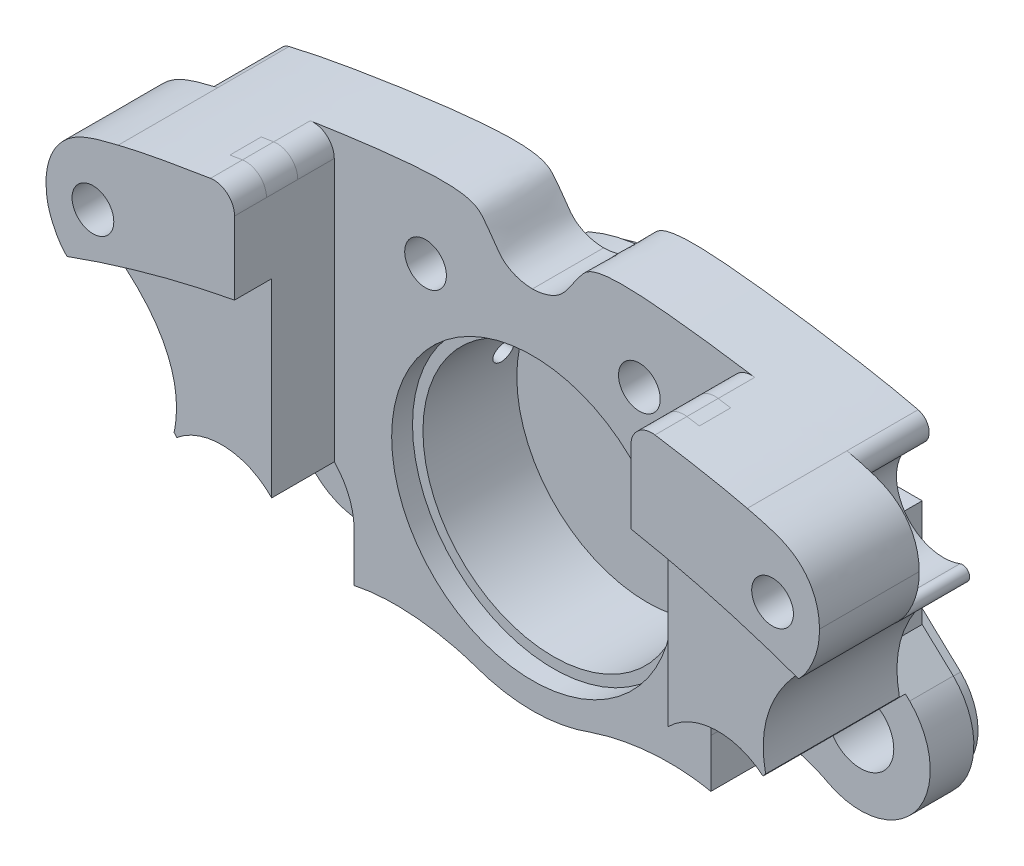
SolidWorks part; units mm, degrees
material "Plain Carbon Steel"
ref_plane "Front Plane" through (0, 0, 0) normal (0, 0, 1) x (1, 0, 0)
ref_plane "Top Plane" through (0, 0, 0) normal (0, 1, 0) x (1, 0, 0)
ref_plane "Right Plane" through (0, 0, 0) normal (1, 0, 0) x (0, 0, -1)
sketch "Sketch1" plane through (0, 0, 0) normal (0, 0, 1) x (1, 0, 0)
  circle A0 centre (0, 0) radius 9.7028
  dimension "D1" = 19.4056
extrude "Boss-Extrude1" add sketch "Sketch1" along normal blind 4.8514
sketch "Sketch2" plane through (0, 0, 4.8514) normal (0, 0, 1) x (1, 0, 0)
  line L0 (0, 15.875) -> (0, -12.065) construction
  line L1 (-30.226, -12.065) -> (30.226, -12.065) construction
  line L2 (-13.4704, 13.4704) -> (-35.3447, -6.9463)
  line L3 (13.4704, 13.4704) -> (35.3447, -6.9463)
  line L4 (0, 0) -> (13.4704, 13.4704) construction
  line L5 (0, 0) -> (-13.4704, 13.4704) construction
  line L8 (15.9939, -16.129) -> (17.3992, -16.129) construction
  line L14 (-17.3992, -16.129) -> (-15.9939, -16.129) construction
  arc A1 (-6.8392, -17.78) -> (6.8392, -17.78) centre (0, 0) ccw
  arc A4 (26.7503, -18.415) -> (35.3447, -6.9463) centre (30.226, -12.065) ccw
  arc A5 (-35.3447, -6.9463) -> (-26.7503, -18.415) centre (-30.226, -12.065) ccw
  arc A7 (13.4704, 13.4704) -> (-13.4704, 13.4704) centre (0, 0) ccw
  spline S0 degree 3 poles (-26.7503, -18.415) (-20.9125, -15.2196) (-12.826, -15.7036) (-6.8392, -17.78) knots 0 0 0 0 1 1 1 1
  spline S1 degree 3 poles (26.7503, -18.415) (20.9125, -15.2196) (12.826, -15.7036) (6.8392, -17.78) knots 0 0 0 0 1 1 1 1
  dimension "D2" = 38.1
  dimension "D6" = 6.35
  dimension "D3" = 27.94
  dimension "D4" = 60.452
  dimension "D5" = 30.226
  dimension "D9" = 17.78
extrude "Boss-Extrude2" add sketch "Sketch2" along normal blind 1.778
sketch "Sketch3" plane through (0, 0, 6.6294) normal (0, 0, 1) x (1, 0, 0)
  line L0 (-14.3527, 14.3841) -> (-18.4698, 10.5414)
  line L1 (36.2267, -6.0322) -> (32.4398, -2.4977)
  line L2 (18.4698, 10.5414) -> (14.3527, 14.3841)
  line L6 (0, 19.05) -> (0, -19.05) construction
  line L7 (18.4698, 10.5414) -> (32.4398, 10.5414)
  line L8 (32.4398, 10.5414) -> (32.4398, -2.4977)
  line L9 (-32.4398, 10.5414) -> (-32.4398, -2.4977)
  line L10 (-18.4698, 10.5414) -> (-32.4398, 10.5414)
  line L11 (-32.4398, -2.4977) -> (-36.2267, -6.0322)
  arc A0 (-36.2267, -6.0322) -> (-26.4195, -19.6751) centre (-30.226, -12.065) ccw
  arc A1 (-7.0511, -19.0574) -> (7.0511, -19.0574) centre (0, 0) ccw
  arc A2 (26.4195, -19.6751) -> (36.2267, -6.0322) centre (30.226, -12.065) ccw
  arc A3 (14.3527, 14.3841) -> (-14.3527, 14.3841) centre (0, 0) ccw
  circle A12 centre (0, 0) radius 15.875 construction
  spline S6 degree 3 poles (-26.4195, -19.6751) (-25.7261, -19.2934) (-24.2904, -18.6475) (-21.15, -17.7332) (-17.755, -17.383) (-14.3154, -17.5158) (-11.771, -17.8352) (-9.7297, -18.2634) (-8.1656, -18.6925) (-7.4233, -18.9297) (-7.0511, -19.0574) knots 0 0 0 0 0.124858 0.249716 0.499432 0.62429 0.749148 0.874006 0.936435 0.998864 0.998864 0.998864 0.998864
  spline S7 degree 3 poles (7.0511, -19.0574) (7.4233, -18.9297) (8.1656, -18.6925) (9.7297, -18.2634) (11.771, -17.8352) (14.3154, -17.5158) (17.755, -17.383) (21.15, -17.7332) (24.2904, -18.6475) (25.7261, -19.2934) (26.4195, -19.6751) knots 0.001136 0.001136 0.001136 0.001136 0.063565 0.125994 0.250852 0.37571 0.500568 0.750284 0.875142 1 1 1 1
  dimension "D3" = 31.75
  dimension "D4" = 13.97
extrude "Boss-Extrude3" add sketch "Sketch3" along normal blind 6.35
sketch "Sketch5" plane through (0, 0, 12.9794) normal (0, 0, 1) x (1, 0, 0)
  line L0 (-41.3748, 17.9058) -> (0, 17.9058) construction
  line L1 (0, 0) -> (0, 17.9058) construction
  line L2 (0, 17.9058) -> (0, 24.1687) construction
  line L3 (1.2486, 24.1687) -> (-1.2486, 24.1687) construction
  line L4 (-35.6955, -5.5467) -> (-36.0146, -5.1665)
  line L5 (35.6955, -5.5467) -> (36.0146, -5.1665)
  line L7 (-30.226, -12.065) -> (30.226, -12.065) construction
  line L8 (-21.717, -12.065) -> (-21.717, -17.9655)
  line L9 (21.717, -12.065) -> (21.717, -17.9655)
  arc A0 (-43.3944, 12.5595) -> (-38.6973, 22.9547) centre (-41.3748, 17.9058) ccw
  arc A1 (-43.3944, 12.5595) -> (-44.0085, 10.9339) centre (-43.7015, 11.7467) ccw
  arc A2 (43.3944, 12.5595) -> (44.0085, 10.9339) centre (43.7015, 11.7467) cw
  arc A3 (-7.0511, -19.0574) -> (7.0511, -19.0574) centre (0, 0) ccw construction
  arc A4 (38.2982, 26.2485) -> (38.6973, 22.9547) centre (37.8646, 24.5249) cw
  arc A5 (-38.2982, 26.2485) -> (-38.6973, 22.9547) centre (-37.8646, 24.5249) ccw
  arc A6 (43.3944, 12.5595) -> (38.6973, 22.9547) centre (41.3748, 17.9058) cw
  arc A7 (-7.0511, -19.0574) -> (7.0511, -19.0574) centre (0, 0) ccw
  arc A8 (35.6955, -5.5467) -> (21.717, -12.065) centre (30.226, -12.065) ccw
  arc A9 (-21.717, -12.065) -> (-35.6955, -5.5467) centre (-30.226, -12.065) ccw
  arc A10 (-36.2267, -6.0322) -> (-26.4195, -19.6751) centre (-30.226, -12.065) ccw construction
  arc A11 (26.4195, -19.6751) -> (36.2267, -6.0322) centre (30.226, -12.065) ccw construction
  spline S0 degree 3 poles (-38.2982, 26.2485) (-33.1754, 27.5373) (-13.115, 30.6549) (-7.0965, 29.9705) (-4.5847, 26.9765) (-3.9197, 25.0203) (-1.0614, 24.1687) (0, 24.1687) knots 0.095992 0.095992 0.095992 0.095992 0.290427 0.440824 0.493566 0.817843 1 1 1 1
  spline S1 degree 3 poles (-44.0085, 10.9339) (-41.4119, 8.9019) (-37.0603, 4.9292) (-35.1847, -1.262) (-36.0146, -5.1665) knots 0.120959 0.120959 0.120959 0.120959 0.469292 0.87789 0.87789 0.87789 0.87789
  spline S2 degree 3 poles (44.0085, 10.9339) (41.4119, 8.9019) (37.0603, 4.9292) (35.1847, -1.262) (36.0146, -5.1665) knots 0.120959 0.120959 0.120959 0.120959 0.469292 0.87789 0.87789 0.87789 0.87789
  spline S3 degree 3 poles (38.2982, 26.2485) (33.1754, 27.5373) (13.115, 30.6549) (7.0965, 29.9705) (4.5847, 26.9765) (3.9197, 25.0203) (1.0614, 24.1687) (0, 24.1687) knots 0.095992 0.095992 0.095992 0.095992 0.290427 0.440824 0.493566 0.817843 1 1 1 1
  spline S5 degree 3 poles (-1496.6618, -2632.8795) (-1.4561, -201.3954) (-67.99, -31.3706) (-21.15, -17.7332) (-17.755, -17.383) (-14.3154, -17.5158) (-11.771, -17.8352) (-9.7297, -18.2634) (16.5073, -25.463) (-0.039, -56.3041) (2811.2429, -1046.1778) knots -6.949708 -6.949708 -6.949708 -6.949708 0.124858 0.249716 0.499432 0.62429 0.749148 0.874006 0.936435 4.938101 4.938101 4.938101 4.938101 only from (-26.4195, -19.6751) to (-7.0511, -19.0574) construction
  spline S6 degree 3 poles (7.0511, -19.0574) (7.4233, -18.9297) (8.1656, -18.6925) (9.7297, -18.2634) (11.771, -17.8352) (14.3154, -17.5158) (17.6851, -17.3857) (20.1633, -17.6317) (21.717, -17.9655) knots 0.001136 0.001136 0.001136 0.001136 0.063565 0.125994 0.250852 0.37571 0.500568 0.740144 0.740144 0.740144 0.740144
  spline S7 degree 3 poles (-21.717, -17.9655) (-20.1633, -17.6317) (-17.6851, -17.3857) (-14.3154, -17.5158) (-11.771, -17.8352) (-9.7297, -18.2634) (-8.1656, -18.6925) (-7.4233, -18.9297) (-7.0511, -19.0574) knots 0.259856 0.259856 0.259856 0.259856 0.499432 0.62429 0.749148 0.874006 0.936435 0.998864 0.998864 0.998864 0.998864
  dimension "D1" = 130
  dimension "D2" = 130
extrude "Boss-Extrude6" add sketch "Sketch5" along normal blind 8.6614
sketch "Sketch6" plane through (0, 0, 21.6408) normal (0, 0, 1) x (1, 0, 0)
  line L0 (0, 0) -> (0, 15.7134) construction
  line L2 (-36.0146, -5.1665) -> (-35.6955, -5.5467) construction
  line L3 (-36.0146, -5.1665) -> (-35.6955, -5.5467)
  line L4 (-36.0146, -5.1665) -> (-35.6955, -5.5467)
  line L5 (35.6955, -5.5467) -> (36.0146, -5.1665) construction
  line L6 (35.6955, -5.5467) -> (36.0146, -5.1665)
  line L11 (-21.717, -12.065) -> (-21.717, -17.9655)
  line L12 (-21.717, -12.065) -> (-21.717, -17.9655)
  line L13 (21.717, -17.9655) -> (21.717, -12.065)
  line L14 (21.717, -17.9655) -> (21.717, -12.065)
  line L15 (35.6955, -5.5467) -> (36.0146, -5.1665)
  arc A0 (-7.0511, -19.0574) -> (7.0511, -19.0574) centre (0, 0) ccw construction
  arc A2 (-7.0511, -19.0574) -> (7.0511, -19.0574) centre (0, 0) ccw
  arc A9 (-38.2982, 26.2485) -> (-38.6973, 22.9547) centre (-37.8646, 24.5249) ccw
  arc A10 (-43.3944, 12.5595) -> (-38.6973, 22.9547) centre (-41.3748, 17.9058) ccw
  arc A11 (-43.3944, 12.5595) -> (-44.0085, 10.9339) centre (-43.7015, 11.7467) ccw
  arc A12 (-21.717, -12.065) -> (-35.6955, -5.5467) centre (-30.226, -12.065) ccw
  arc A14 (-21.717, -12.065) -> (-35.6955, -5.5467) centre (-30.226, -12.065) ccw
  arc A15 (44.0085, 10.9339) -> (43.3944, 12.5595) centre (43.7015, 11.7467) ccw
  arc A16 (38.6973, 22.9547) -> (43.3944, 12.5595) centre (41.3748, 17.9058) ccw
  arc A17 (38.6973, 22.9547) -> (38.2982, 26.2485) centre (37.8646, 24.5249) ccw
  arc A19 (-7.0511, -19.0574) -> (7.0511, -19.0574) centre (0, 0) ccw
  arc A25 (35.6955, -5.5467) -> (21.717, -12.065) centre (30.226, -12.065) ccw
  arc A26 (35.6955, -5.5467) -> (21.717, -12.065) centre (30.226, -12.065) ccw
  spline S0 degree 3 poles (-38.2982, 26.2485) (-40.3087, 25.7427) (-44.7917, 24.769) (-47.0898, 20.7135) (-47.0898, 17.9058) knots 0 0 0 0 0.465439 1 1 1 1
  spline S1 degree 3 poles (-47.0898, 17.9058) (-47.0898, 16.2266) (-46.4199, 13.9412) (-45.0511, 11.7499) (-44.0085, 10.9339) knots 0 0 0 0 0.544279 1 1 1 1
  spline S2 degree 3 poles (47.0898, 17.9058) (47.0898, 16.2266) (46.4199, 13.9412) (45.0511, 11.7499) (44.0085, 10.9339) knots 0 0 0 0 0.544279 1 1 1 1
  spline S3 degree 3 poles (38.2982, 26.2485) (40.3087, 25.7427) (44.7917, 24.769) (47.0898, 20.7135) (47.0898, 17.9058) knots 0 0 0 0 0.465439 1 1 1 1
  spline S4 degree 3 poles (-657.2117, 1910.6164) (-193.2792, -28.4777) (64.9588, 100.6233) (-94.862, -144.8705) (-2021.4839, -219.0001) knots -4.624316 -4.624316 -4.624316 -4.624316 0.469292 5.21147 5.21147 5.21147 5.21147 only from (-44.0085, 10.9339) to (-36.0146, -5.1665) construction
  spline S6 degree 3 poles (-2183.245, 2077.1816) (166.4827, 62.4672) (0.5629, 11.8331) (-4.5847, 26.9765) (-7.0965, 29.9705) (-30.8647, 32.6733) (-341.1745, -36.5716) (2935.9323, 415.7326) knots -3.67352 -3.67352 -3.67352 -3.67352 0.278149 0.602426 0.655168 0.805566 2.172513 2.172513 2.172513 2.172513 only from (0, 24.1687) to (-38.2982, 26.2485)
  spline S7 degree 3 poles (-408.6307, 942.0868) (-142.5011, -5.0132) (25.7847, 65.0404) (-66.3745, -98.2734) (-1022.8759, -166.7155) knots -3.564937 -3.564937 -3.564937 -3.564937 0.469292 4.198398 4.198398 4.198398 4.198398 only from (-44.0085, 10.9339) to (-36.0146, -5.1665)
  spline S8 degree 3 poles (773.9984, -623.6344) (-88.6459, -105.5622) (-56.1182, -15.9019) (-14.3154, -17.5158) (-11.771, -17.8352) (-9.7297, -18.2634) (8.744, -23.3327) (6.1469, -39.711) (927.5284, -374.7025) knots -5.320743 -5.320743 -5.320743 -5.320743 0.499432 0.62429 0.749148 0.874006 0.936435 3.698622 3.698622 3.698622 3.698622 only from (-21.717, -17.9655) to (-7.0511, -19.0574)
  spline S10 degree 3 poles (1022.878, -166.7156) (66.3745, -98.2735) (-25.7847, 65.0403) (142.501, -5.0132) (408.6302, 942.085) knots -3.199551 -3.199551 -3.199551 -3.199551 0.529557 4.563784 4.563784 4.563784 4.563784 only from (36.0146, -5.1665) to (44.0085, 10.9339)
  spline S11 degree 3 poles (-2936.0853, 415.7537) (341.1832, -36.5735) (30.865, 32.6733) (7.0965, 29.9705) (4.5847, 26.9765) (-0.5628, 11.8332) (-166.4811, 62.4666) (2183.2062, 2077.1484) knots -1.076542 -1.076542 -1.076542 -1.076542 0.290427 0.440824 0.493566 0.817843 4.76949 4.76949 4.76949 4.76949 only from (38.2982, 26.2485) to (0, 24.1687)
  spline S12 degree 3 poles (0, 24.1687) (-1.0614, 24.1687) (-3.9197, 25.0203) (-4.5847, 26.9765) (-7.0965, 29.9705) (-13.115, 30.6549) (-33.1754, 27.5373) (-38.2982, 26.2485) knots 0.095992 0.095992 0.095992 0.095992 0.278149 0.602426 0.655168 0.805566 1 1 1 1
  spline S13 degree 3 poles (2021.4462, -218.9987) (94.861, -144.8689) (-64.9585, 100.6237) (193.281, -28.4786) (657.2209, 1910.6551) knots -4.212589 -4.212589 -4.212589 -4.212589 0.529557 5.6232 5.6232 5.6232 5.6232 only from (36.0146, -5.1665) to (44.0085, 10.9339) construction
  spline S14 degree 3 poles (-44.0085, 10.9339) (-41.4119, 8.9019) (-37.0603, 4.9292) (-35.1847, -1.262) (-36.0146, -5.1665) knots 0.120959 0.120959 0.120959 0.120959 0.469292 0.87789 0.87789 0.87789 0.87789
  spline S15 degree 3 poles (-1868.6977, -712.6953) (-3.4507, -48.9434) (-13.3148, -24.587) (9.7297, -18.2634) (11.771, -17.8352) (14.3154, -17.5158) (66.5225, -15.5003) (104.6343, -157.023) (-1642.0572, -1120.0359) knots -3.428399 -3.428399 -3.428399 -3.428399 0.063565 0.125994 0.250852 0.37571 0.500568 7.831491 7.831491 7.831491 7.831491 only from (7.0511, -19.0574) to (21.717, -17.9655) construction
  spline S16 degree 3 poles (1642.0265, -1120.019) (-104.6338, -157.0214) (-66.5222, -15.5003) (-14.3154, -17.5158) (-11.771, -17.8352) (-9.7297, -18.2634) (13.3145, -24.5869) (3.451, -48.9427) (1868.6163, -712.6663) knots -6.831448 -6.831448 -6.831448 -6.831448 0.499432 0.62429 0.749148 0.874006 0.936435 4.428348 4.428348 4.428348 4.428348 only from (-21.717, -17.9655) to (-7.0511, -19.0574) construction
  spline S17 degree 3 poles (38.2982, 26.2485) (33.1754, 27.5373) (13.115, 30.6549) (7.0965, 29.9705) (4.5847, 26.9765) (3.9197, 25.0203) (1.0614, 24.1687) (0, 24.1687) knots 0.095992 0.095992 0.095992 0.095992 0.290427 0.440824 0.493566 0.817843 1 1 1 1
  spline S18 degree 3 poles (36.0146, -5.1665) (35.1847, -1.262) (37.0603, 4.9292) (41.4119, 8.9019) (44.0085, 10.9339) knots 0.120959 0.120959 0.120959 0.120959 0.529557 0.87789 0.87789 0.87789 0.87789
  spline S19 degree 3 poles (7.0511, -19.0574) (7.4233, -18.9297) (8.1656, -18.6925) (9.7297, -18.2634) (11.771, -17.8352) (14.3154, -17.5158) (17.6851, -17.3857) (20.1633, -17.6317) (21.717, -17.9655) knots 0.001136 0.001136 0.001136 0.001136 0.063565 0.125994 0.250852 0.37571 0.500568 0.740144 0.740144 0.740144 0.740144
  spline S20 degree 3 poles (-21.717, -17.9655) (-20.1633, -17.6317) (-17.6851, -17.3857) (-14.3154, -17.5158) (-11.771, -17.8352) (-9.7297, -18.2634) (-8.1656, -18.6925) (-7.4233, -18.9297) (-7.0511, -19.0574) knots 0.259856 0.259856 0.259856 0.259856 0.499432 0.62429 0.749148 0.874006 0.936435 0.998864 0.998864 0.998864 0.998864
  spline S26 degree 3 poles (-927.5625, -374.7149) (-6.1469, -39.7114) (-8.7442, -23.3328) (9.7297, -18.2634) (11.771, -17.8352) (14.3154, -17.5158) (56.1182, -15.9019) (88.6459, -105.5622) (-773.9984, -623.6344) knots -2.698656 -2.698656 -2.698656 -2.698656 0.063565 0.125994 0.250852 0.37571 0.500568 6.320743 6.320743 6.320743 6.320743 only from (7.0511, -19.0574) to (21.717, -17.9655)
  dimension "D1" = 0
extrude "Boss-Extrude8" add sketch "Sketch6" along normal blind 7.62
ref_plane "Plane5" through (0, 0, 29.2608) normal (0, 0, 1) x (1, 0, 0)
sketch "Sketch8" plane through (0, 0, 0) normal (0, 0, 1) x (1, 0, 0)
  line L0 (0, 0.0477) -> (0, -110.9255) construction
  line L1 (30.226, -12.065) -> (0, -110.9255) construction
  circle A0 centre (0, -110.9255) radius 103.378
  circle A1 centre (0, -110.9255) radius 142.4868
  circle A2 centre (0, 0.0477) radius 15.875
  arc A3 (44.0085, 10.9339) -> (44.4588, 11.3208) centre (40.0294, 16.0204) ccw
  arc A4 (44.0085, 10.9339) -> (44.4588, 11.3208) centre (40.0294, 16.0204) ccw
  arc A24 (44.0085, 10.9339) -> (44.4588, 11.3208) centre (43.7015, 11.7467) ccw
  arc A25 (44.0085, 10.9339) -> (44.4588, 11.3208) centre (43.7015, 11.7467) ccw
  spline S0 degree 3 poles (-38.2982, 26.2485) (-40.3087, 25.7427) (-44.7917, 24.769) (-47.0898, 20.7135) (-47.0898, 17.9058) knots 0 0 0 0 0.465439 1 1 1 1 construction
  dimension "D3" = 31.75
  dimension "D2" = 103.378
  dimension "D1" = 0
sketch "Sketch9" plane through (0, 0, 29.2608) normal (0, 0, 1) x (1, 0, 0)
  line L1 (-36.0146, -5.1665) -> (-35.6955, -5.5467)
  line L4 (-36.0146, -5.1665) -> (-35.6955, -5.5467)
  line L6 (-21.717, -12.065) -> (-21.717, -17.9655)
  line L7 (-21.717, -12.065) -> (-21.717, -17.9655)
  line L8 (21.717, -17.9655) -> (21.717, -12.065)
  line L9 (21.717, -17.9655) -> (21.717, -12.065)
  line L10 (35.6955, -5.5467) -> (36.0146, -5.1665)
  line L11 (35.6955, -5.5467) -> (36.0146, -5.1665)
  arc A0 (44.5354, 11.3943) -> (-44.5354, 11.3943) centre (0, -110.9255) ccw
  arc A4 (-21.717, -12.065) -> (-35.6955, -5.5467) centre (-30.226, -12.065) ccw
  arc A5 (-21.717, -12.065) -> (-35.6955, -5.5467) centre (-30.226, -12.065) ccw
  arc A6 (-7.0511, -19.0574) -> (7.0511, -19.0574) centre (0, 0) ccw
  arc A7 (-7.0511, -19.0574) -> (7.0511, -19.0574) centre (0, 0) ccw
  arc A8 (35.6955, -5.5467) -> (21.717, -12.065) centre (30.226, -12.065) ccw
  arc A9 (35.6955, -5.5467) -> (21.717, -12.065) centre (30.226, -12.065) ccw
  spline S8 degree 3 poles (-1945.4334, 279.8837) (280.2808, -23.0655) (28.498, 32.4041) (7.0965, 29.9705) (4.5847, 26.9765) (0.0126, 13.5261) (-130.9865, 51.8462) (1427.7462, 1422.0243) knots -0.920185 -0.920185 -0.920185 -0.920185 0.290427 0.440824 0.493566 0.817843 4.285577 4.285577 4.285577 4.285577 only from (38.2982, 26.2485) to (0, 24.1687)
  spline S9 degree 3 poles (-1427.7778, 1422.0521) (130.9882, 51.8467) (-0.0126, 13.526) (-4.5847, 26.9765) (-7.0965, 29.9705) (-28.498, 32.4041) (-280.2788, -23.065) (1945.4024, 279.8795) knots -3.189608 -3.189608 -3.189608 -3.189608 0.278149 0.602426 0.655168 0.805566 2.016171 2.016171 2.016171 2.016171 only from (0, 24.1687) to (-38.2982, 26.2485)
  spline S10 degree 3 poles (-1203.0636, 1651.5353) (93.7878, -75.1517) (-154.8007, 172.9552) (27.8634, -187.1962) (1943.2757, 119.6036) knots -6.046521 -6.046521 -6.046521 -6.046521 0.465439 8.002474 8.002474 8.002474 8.002474 only from (-38.2982, 26.2485) to (-47.0898, 17.9058)
  spline S11 degree 3 poles (767.238, 1844.5312) (-10.0436, 60.6724) (-97.6366, 8.3146) (18.3471, -16.6051) (1728.6586, 935.753) knots -8.30307 -8.30307 -8.30307 -8.30307 0.544279 8.765796 8.765796 8.765796 8.765796 only from (-47.0898, 17.9058) to (-44.0085, 10.9339)
  spline S12 degree 3 poles (-408.6307, 942.0868) (-142.5011, -5.0132) (25.7847, 65.0404) (-66.3745, -98.2734) (-1022.8759, -166.7155) knots -3.564937 -3.564937 -3.564937 -3.564937 0.469292 4.198398 4.198398 4.198398 4.198398 only from (-44.0085, 10.9339) to (-36.0146, -5.1665)
  spline S14 degree 3 poles (-1728.6926, 935.7719) (-18.3478, -16.6052) (97.6372, 8.3145) (10.0431, 60.6727) (-767.2495, 1844.5577) knots -7.765851 -7.765851 -7.765851 -7.765851 0.455721 9.303114 9.303114 9.303114 9.303114 only from (44.0085, 10.9339) to (47.0898, 17.9058)
  spline S15 degree 3 poles (-1943.2768, 119.6038) (-27.8634, -187.1963) (154.8004, 172.9546) (-93.787, -75.1509) (1203.05, 1651.5172) knots -7.002475 -7.002475 -7.002475 -7.002475 0.534561 7.046498 7.046498 7.046498 7.046498 only from (47.0898, 17.9058) to (38.2982, 26.2485)
  spline S16 degree 3 poles (38.2982, 26.2485) (33.1754, 27.5373) (13.115, 30.6549) (7.0965, 29.9705) (4.5847, 26.9765) (3.9197, 25.0203) (1.0614, 24.1687) (0, 24.1687) knots 0.095992 0.095992 0.095992 0.095992 0.290427 0.440824 0.493566 0.817843 1 1 1 1
  spline S17 degree 3 poles (0, 24.1687) (-1.0614, 24.1687) (-3.9197, 25.0203) (-4.5847, 26.9765) (-7.0965, 29.9705) (-13.115, 30.6549) (-33.1754, 27.5373) (-38.2982, 26.2485) knots 0.095992 0.095992 0.095992 0.095992 0.278149 0.602426 0.655168 0.805566 1 1 1 1
  spline S18 degree 3 poles (-38.2982, 26.2485) (-40.3087, 25.7427) (-44.7917, 24.769) (-47.0898, 20.7135) (-47.0898, 17.9058) knots 0 0 0 0 0.465439 1 1 1 1
  spline S19 degree 3 poles (-47.0898, 17.9058) (-47.0898, 16.2266) (-46.4752, 14.1298) (-45.2723, 12.1122) (-44.5354, 11.3943) knots 0 0 0 0 0.544279 0.917463 0.917463 0.917463 0.917463
  spline S21 degree 3 poles (773.9984, -623.6344) (-88.6459, -105.5622) (-56.1182, -15.9019) (-14.3154, -17.5158) (-11.771, -17.8352) (-9.7297, -18.2634) (8.744, -23.3327) (6.1469, -39.711) (927.5284, -374.7025) knots -5.320743 -5.320743 -5.320743 -5.320743 0.499432 0.62429 0.749148 0.874006 0.936435 3.698622 3.698622 3.698622 3.698622 only from (-21.717, -17.9655) to (-7.0511, -19.0574)
  spline S22 degree 3 poles (44.5354, 11.3943) (45.2723, 12.1122) (46.4752, 14.1298) (47.0898, 16.2266) (47.0898, 17.9058) knots 0.082537 0.082537 0.082537 0.082537 0.455721 1 1 1 1
  spline S23 degree 3 poles (47.0898, 17.9058) (47.0898, 20.7135) (44.7917, 24.769) (40.3087, 25.7427) (38.2982, 26.2485) knots 0 0 0 0 0.534561 1 1 1 1
  spline S24 degree 3 poles (-21.717, -17.9655) (-20.1633, -17.6317) (-17.6851, -17.3857) (-14.3154, -17.5158) (-11.771, -17.8352) (-9.7297, -18.2634) (-8.1656, -18.6925) (-7.4233, -18.9297) (-7.0511, -19.0574) knots 0.259856 0.259856 0.259856 0.259856 0.499432 0.62429 0.749148 0.874006 0.936435 0.998864 0.998864 0.998864 0.998864
  spline S25 degree 3 poles (-927.5625, -374.7149) (-6.1469, -39.7114) (-8.7442, -23.3328) (9.7297, -18.2634) (11.771, -17.8352) (14.3154, -17.5158) (56.1182, -15.9019) (88.6459, -105.5622) (-773.9984, -623.6344) knots -2.698656 -2.698656 -2.698656 -2.698656 0.063565 0.125994 0.250852 0.37571 0.500568 6.320743 6.320743 6.320743 6.320743 only from (7.0511, -19.0574) to (21.717, -17.9655)
  spline S26 degree 3 poles (7.0511, -19.0574) (7.4233, -18.9297) (8.1656, -18.6925) (9.7297, -18.2634) (11.771, -17.8352) (14.3154, -17.5158) (17.6851, -17.3857) (20.1633, -17.6317) (21.717, -17.9655) knots 0.001136 0.001136 0.001136 0.001136 0.063565 0.125994 0.250852 0.37571 0.500568 0.740144 0.740144 0.740144 0.740144
  spline S28 degree 3 poles (1022.878, -166.7156) (66.3745, -98.2735) (-25.7847, 65.0403) (142.501, -5.0132) (408.6302, 942.085) knots -3.199551 -3.199551 -3.199551 -3.199551 0.529557 4.563784 4.563784 4.563784 4.563784 only from (36.0146, -5.1665) to (44.0085, 10.9339)
  dimension "D1" = 260.35
  dimension "D2" = 0
extrude "Boss-Extrude9" add sketch "Sketch9" along normal blind 4.5212 contours S22 S23 S16 S17 S18 S19 A0 region at (0, 21.9757, 29.2608)
sketch "Sketch10" plane through (0, 0, 0) normal (0, 1, 0) x (1, 0, 0)
  line L1 (-24.13, -45.9232) -> (24.13, -45.9232)
  line L2 (-24.13, -45.9232) -> (-24.13, -21.6408)
  line L3 (-24.13, -21.6408) -> (24.13, -21.6408)
  line L4 (24.13, -45.9232) -> (24.13, -21.6408)
  line L5 (-24.13, -45.9232) -> (24.13, -21.6408) construction
  line L6 (-24.13, -21.6408) -> (24.13, -45.9232) construction
  point P0 (0, -33.782)
  dimension "D2" = 48.26
extrude "Cut-Extrude1" cut sketch "Sketch10" against normal mid plane 127
sketch "Sketch11" plane through (0, 0, 4.8514) normal (0, 0, -1) x (-1, 0, 0)
  line L0 (0, 0) -> (0, 20.32) construction
  line L1 (-13.0136, 20.32) -> (13.0136, 20.32) construction
  circle A0 centre (-13.0136, 20.32) radius 5.08
  circle A1 centre (13.0136, 20.32) radius 5.08
  arc A3 (13.4704, 13.4704) -> (-13.4704, 13.4704) centre (0, 0) ccw construction
  dimension "D1" = 10.16
extrude "Cut-Extrude2" cut sketch "Sketch11" against normal up to surface (8.128 mm away) up to face at (1.4431, 10.3095, 12.9794)
sketch "Sketch12" plane through (0, 0, 21.6408) normal (0, 0, -1) x (-1, 0, 0)
  line L0 (0, 0) -> (0, 32.3308) construction
  circle A2 centre (41.3748, 17.9058) radius 2.54
  circle A3 centre (-41.3748, 17.9058) radius 2.54
  dimension "D1" = 5.08
extrude "Cut-Extrude3" cut sketch "Sketch12" against normal through all
sketch "Sketch13" plane through (0, 0, 12.9794) normal (0, 0, -1) x (-1, 0, 0)
  line L0 (0, 0) -> (0, 20.32) construction
  line L1 (-13.0175, 20.32) -> (13.0175, 20.32) construction
  circle A2 centre (13.0175, 20.32) radius 2.54
  circle A3 centre (-13.0175, 20.32) radius 2.54
  dimension "D1" = 5.08
  dimension "D2" = 20.32
  dimension "D3" = 26.035
extrude "Cut-Extrude4" cut sketch "Sketch13" against normal through all
sketch "Sketch14" plane through (0, 0, 0) normal (0, 1, 0) x (1, 0, 0)
  line L0 (0, -21.6408) -> (0, -27.9908) construction
  line L1 (-28.575, -29.8958) -> (28.575, -29.8958)
  line L2 (-28.575, -29.8958) -> (-28.575, -26.0858)
  line L3 (-28.575, -26.0858) -> (28.575, -26.0858)
  line L4 (28.575, -29.8958) -> (28.575, -26.0858)
  line L5 (-28.575, -29.8958) -> (28.575, -26.0858) construction
  line L6 (-28.575, -26.0858) -> (28.575, -29.8958) construction
  point P0 (0, -27.9908)
  dimension "D1" = 57.15
  dimension "D2" = 3.81
  dimension "D3" = 6.35
split line "Split Line1"
sketch "Sketch15" plane through (0, 0, 0) normal (0, 0, -1) x (-1, 0, 0)
  circle A0 centre (0, 0) radius 15.875
  dimension "D1" = 31.75
extrude "Cut-Extrude5" cut sketch "Sketch15" along normal blind 13.97 from surface starting at face at (10.4775, 20.32, 21.6408)
sketch "Sketch16" plane through (-32.4398, 0, 0) normal (-1, 0, 0) x (0, 0, 1)
  line L0 (12.9794, 10.5414) -> (6.6294, -2.4977) construction
  line L1 (6.6294, 10.5414) -> (12.9794, -2.4977) construction
  line L4 (12.9794, 10.5414) -> (6.6294, 10.5414)
  line L5 (6.6294, 10.5414) -> (6.6294, -2.4977)
  line L6 (6.6294, -2.4977) -> (12.9794, -2.4977)
  line L7 (6.6294, 10.5414) -> (6.6294, -2.4977)
  line L8 (12.9794, 10.5414) -> (6.6294, 10.5414) construction
  line L9 (12.9794, -2.4977) -> (12.9794, 10.5414)
  line L10 (6.6294, -2.4977) -> (12.9794, -2.4977) construction
  line L11 (12.9794, -2.4977) -> (12.9794, 10.5414)
  circle A0 centre (9.8044, 4.0218) radius 1.27
  dimension "D2" = 2.54
  dimension "D1" = 0
extrude "Cut-Extrude6" cut sketch "Sketch16" against normal through all contours A0 region at (-32.4398, 4.0218, 9.8044)
fillet "Fillet5" radius 2.54 6 edges at (24.13, 28.8083, 31.8389) (24.13, 28.8083, 27.9908) (24.13, 28.8083, 23.8633) (-24.13, 28.8083, 31.8389) (-24.13, 28.8083, 23.8633) (-24.13, 28.8083, 27.9908)
sketch "Sketch17" plane through (0, 0, 21.6408) normal (0, 0, 1) x (1, 0, 0)
  circle A0 centre (0, 0) radius 17.145
  dimension "D1" = 34.29
extrude "Cut-Extrude7" cut sketch "Sketch17" against normal blind 2.54
sketch "Sketch18" plane through (0, 0, 21.6408) normal (0, 0, 1) x (1, 0, 0)
  circle A0 centre (-30.226, -12.065) radius 4.064
  circle A1 centre (30.226, -12.065) radius 4.064
  dimension "D1" = 60.452
extrude "Cut-Extrude8" cut sketch "Sketch18" against normal through all
sketch "Sketch19" plane through (0, 0, 12.9794) normal (0, 0, 1) x (1, 0, 0)
  line L0 (35.7004, -5.5409) -> (35.6955, -5.5467) construction
  line L1 (21.717, -12.065) -> (21.717, -17.9655) construction
  line L2 (36.2267, -6.0322) -> (35.7004, -5.5409) construction
  line L3 (-21.717, -17.9655) -> (-21.717, -12.065) construction
  line L4 (-35.6955, -5.5467) -> (-35.7004, -5.5409) construction
  line L5 (-35.7004, -5.5409) -> (-36.2267, -6.0322) construction
  line L6 (35.7004, -5.5409) -> (35.6955, -5.5467)
  line L7 (21.717, -12.065) -> (21.717, -17.9655)
  line L8 (36.2267, -6.0322) -> (35.7004, -5.5409)
  line L9 (-21.717, -17.9655) -> (-21.717, -12.065)
  line L10 (-35.6955, -5.5467) -> (-35.7004, -5.5409)
  line L11 (-35.7004, -5.5409) -> (-36.2267, -6.0322)
  arc A0 (35.6955, -5.5467) -> (21.717, -12.065) centre (30.226, -12.065) ccw construction
  arc A1 (26.4195, -19.6751) -> (36.2267, -6.0322) centre (30.226, -12.065) ccw construction
  arc A2 (-21.717, -12.065) -> (-35.6955, -5.5467) centre (-30.226, -12.065) ccw construction
  arc A3 (-36.2267, -6.0322) -> (-26.4195, -19.6751) centre (-30.226, -12.065) ccw construction
  arc A4 (35.6955, -5.5467) -> (21.717, -12.065) centre (30.226, -12.065) ccw
  arc A5 (26.4195, -19.6751) -> (36.2267, -6.0322) centre (30.226, -12.065) ccw
  arc A6 (-21.717, -12.065) -> (-35.6955, -5.5467) centre (-30.226, -12.065) ccw
  arc A7 (-36.2267, -6.0322) -> (-26.4195, -19.6751) centre (-30.226, -12.065) ccw
  spline S0 degree 3 poles (2953.6666, 598.3382) (-210.4377, -244.2184) (-34.8546, -1.4275) (67.9899, -31.3706) (1.4564, -201.3947) (1496.6526, -2632.8646) knots -8.406046 -8.406046 -8.406046 -8.406046 0.750284 0.875142 7.949694 7.949694 7.949694 7.949694 only from (21.717, -17.9655) to (26.4195, -19.6751) construction
  spline S1 degree 3 poles (-1496.6642, -2632.8834) (-1.4561, -201.3956) (-67.99, -31.3706) (34.854, -1.4276) (210.4337, -244.2129) (-2953.5572, 598.3091) knots -6.949712 -6.949712 -6.949712 -6.949712 0.124858 0.249716 9.40594 9.40594 9.40594 9.40594 only from (-26.4195, -19.6751) to (-21.717, -17.9655) construction
  spline S2 degree 3 poles (21.717, -17.9655) (21.7828, -17.9796) (22.6564, -18.1718) (24.2904, -18.6475) (25.7261, -19.2934) (26.4195, -19.6751) knots 0.740144 0.740144 0.740144 0.740144 0.750284 0.875142 1 1 1 1
  spline S3 degree 3 poles (-26.4195, -19.6751) (-25.7261, -19.2934) (-24.2904, -18.6475) (-22.6564, -18.1718) (-21.7828, -17.9796) (-21.717, -17.9655) knots 0 0 0 0 0.124858 0.249716 0.259856 0.259856 0.259856 0.259856
extrude "Cut-Extrude9" cut sketch "Sketch19" against normal blind 1.0414
ref_plane "Plane6" through (0, -20.32, 0) normal (0, -1, 0) x (-1, 0, 0)
sketch "Sketch20" plane through (0, 0, 4.8514) normal (0, 0, -1) x (-1, 0, 0)
  line L0 (-30.226, -12.065) -> (30.226, -12.065)
